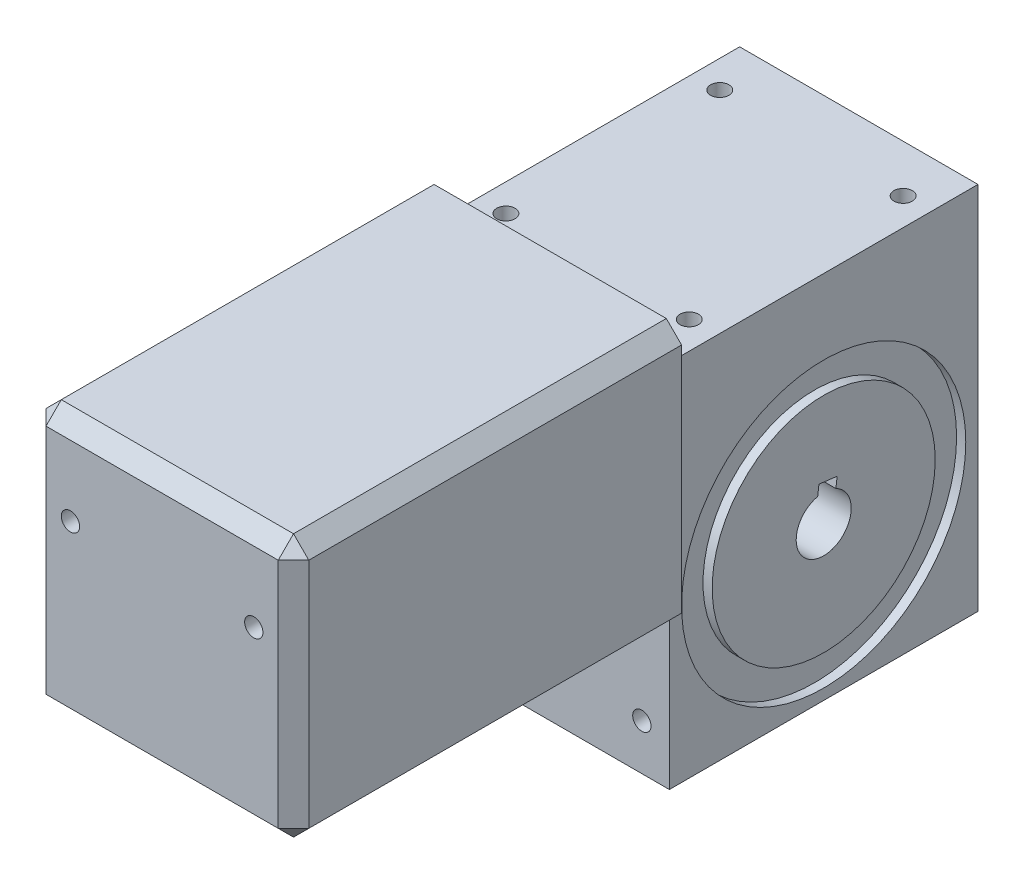
SolidWorks part; units mm, degrees
ref_plane "前视基准面" through (0, 0, 0) normal (0, 0, 1) x (1, 0, 0)
ref_plane "上视基准面" through (0, 0, 0) normal (0, 1, 0) x (1, 0, 0)
ref_plane "右视基准面" through (0, 0, 0) normal (1, 0, 0) x (0, 0, -1)
sketch "草图1" plane through (0, 0, 0) normal (0, 1, 0) x (1, 0, 0)
  line L0 (0, 151.4127) -> (0, -91.8329) construction
  line L1 (-39, 0) -> (39, 0)
  line L2 (39, 0) -> (39, 101)
  line L3 (39, 101) -> (-39, 101)
  line L4 (-39, 101) -> (-39, 0)
  point P3 (39, 50.5)
  point P6 (0, 0)
  dimension "D1" = 78
  dimension "D2" = 101
extrude "凸台-拉伸1" add sketch "草图1" along normal blind 121
sketch "草图4" plane through (0, 0, 0) normal (0, 0, 1) x (1, 0, 0)
  line L0 (-39, 0) -> (39, 0) construction
  line L1 (-43, 133) -> (43, 133)
  line L2 (-43, 133) -> (-43, 47)
  line L3 (-43, 47) -> (43, 47)
  line L4 (43, 133) -> (43, 47)
  line L5 (-43, 133) -> (43, 47) construction
  line L6 (-43, 47) -> (43, 133) construction
  line L7 (0, -33.0572) -> (0, 154.5156) construction
  point P0 (0, 90)
  dimension "D1" = 86
  dimension "D2" = 86
  dimension "D3" = 90
extrude "凸台-拉伸2" add sketch "草图4" along normal blind 127
sketch "草图5" plane through (0, 0, 0) normal (1, 0, 0) x (0, 0, -1)
  line L0 (0, 0) -> (101, 0) construction
  line L3 (0, 121) -> (101, 121) construction
  line L4 (50.5, 121) -> (50.5, 0) construction
  line L5 (50.5, 0) -> (50.5, -32.6217) construction
  circle A0 centre (50.5, 50) radius 7
  dimension "D2" = 14
  dimension "D1" = 50
extrude "切除-拉伸1" cut sketch "草图5" along normal through all and the other way through all
chamfer "倒角1" distance 5 angle 45 8 edges at (43, 47, 63.5) (-43, 47, 63.5) (-43, 90, 127) (-43, 133, 63.5) (0, 133, 127) (0, 47, 127) (43, 90, 127) (43, 133, 63.5)
sketch "草图6" plane through (0, 0, -101) normal (0, 0, -1) x (-1, 0, 0)
  line L0 (-39, 50) -> (87.0034, 50) construction
  line L1 (-39, 121) -> (-39, 0) construction
  line L2 (-39, 0) -> (39, 0) construction
  line L3 (0, 121) -> (0, 0) construction
  line L4 (-39, 121) -> (39, 121) construction
  line L5 (0, 0) -> (0, -24.5585) construction
  circle A0 centre (-30, 15) radius 3
  circle A1 centre (30, 15) radius 3
  circle A2 centre (-30, 105) radius 3
  circle A3 centre (30, 105) radius 3
  point P4 (-30, 15)
  point P12 (30, 15)
  dimension "D6" = 6
  dimension "D7" = 6
  dimension "D8" = 6
  dimension "D9" = 6
  dimension "D1" = 50
  dimension "D4" = 35
  dimension "D5" = 60
  dimension "D11" = 55
  dimension "D12" = 60
extrude "切除-拉伸2" cut sketch "草图6" against normal up to next
sketch "草图7" plane through (0, 121, 0) normal (0, 1, 0) x (1, 0, 0)
  line L0 (39, 50.5) -> (-39, 50.5) construction
  line L1 (39, 0) -> (39, 101) construction
  line L2 (-39, 101) -> (-39, 0) construction
  line L3 (0, 101) -> (0, 0) construction
  line L4 (39, 101) -> (-39, 101) construction
  line L5 (0, 0) -> (0.3428, -0.3555) construction
  circle A0 centre (30, 85.5) radius 3
  circle A1 centre (30, 15.5) radius 3
  circle A3 centre (-30, 15.5) radius 3
  circle A4 centre (-30, 85.5) radius 3
  dimension "D1" = 6
  dimension "D2" = 60
  dimension "D3" = 70
extrude "切除-拉伸3" cut sketch "草图7" against normal through all
sketch "草图8" plane through (-39, 0, 0) normal (-1, 0, 0) x (0, 0, 1)
  circle A0 centre (-50.5, 50) radius 36.5
  dimension "D1" = 73
sketch "草图9" plane through (39, 0, 0) normal (1, 0, 0) x (0, 0, -1)
  circle A0 centre (50.5, 50) radius 36.5
  dimension "D1" = 73
extrude "切除-拉伸-薄壁1" cut sketch "草图8" against normal blind 3 thin contours A0 thin type one direction wall 10
extrude "切除-拉伸-薄壁2" cut sketch "草图9" against normal blind 3 thin contours A0 thin type one direction wall 10
sketch "KeySketch" plane through (-39, 56.9797, -54.7014) normal (-1, 0, 0) x (0, 0, 1)
  line L0 (5.2901, -15.9136) -> (2.7739, 4.7336) construction
  line L1 (-4.7325, -8.0685) -> (13.1353, -5.891) construction
  line L2 (0.197, 1.0803) -> (-0.204, 4.3707)
  line L4 (5.7519, 5.0965) -> (6.1529, 1.8061)
  line L5 (5.7519, 5.0965) -> (-0.204, 4.3707)
  arc A0 (0.197, 1.0803) -> (6.1529, 1.8061) centre (4.2014, -6.9797) ccw
  circle A1 centre (4.2014, -6.9797) radius 7 construction
  point P10 (2.7739, 4.7336)
  dimension "Diameter" = 18
  dimension "Width" = 6
  dimension "Depth" = 2.8
extrude "Keyway" cut sketch "KeySketch" against normal through all
other "bore with deep pattern keyway din 6886 p1<1>"
